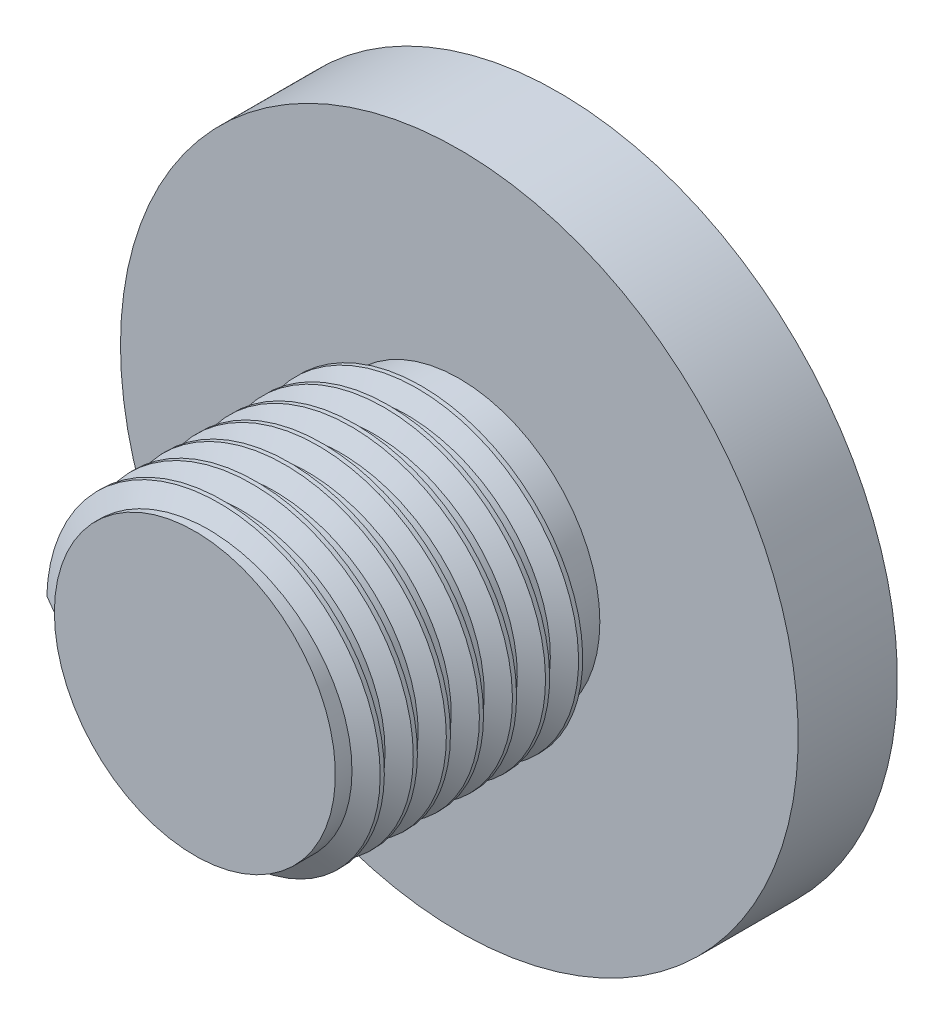
SolidWorks part; units mm, degrees
ref_plane "Plan de face" through (0, 0, 0) normal (0, 0, 1) x (1, 0, 0)
ref_plane "Plan de dessus" through (0, 0, 0) normal (0, 1, 0) x (1, 0, 0)
ref_plane "Plan de droite" through (0, 0, 0) normal (1, 0, 0) x (0, 0, -1)
sketch "Sketch1" plane through (0, 0, 0) normal (0, 0, 1) x (1, 0, 0)
  circle A0 centre (0, 0) radius 4.25
  dimension "D1" = 8.5
extrude "Boss-Extrude1" add sketch "Sketch1" along normal blind 8
sketch "Sketch2" plane through (0, 0, 0) normal (0, 0, -1) x (-1, 0, 0)
  circle A0 centre (0, 0) radius 10.25
  circle A1 centre (0, 0) radius 4.25 construction
  dimension "D1" = 6
extrude "Boss-Extrude2" add sketch "Sketch2" along normal blind 3
thread "Thread1" pitch 1 method extrude profile "Thread Profile1" start angle 0, offset 0, length 7, pitch 1, diameter 8.5
ref_plane "Plane1" through (-4.25, 0, 8) normal (0, -1, 0) x (-1, 0, 0)
sketch "Thread Profile1" plane through (-4.25, 0, 8) normal (0, -1, 0) x (-1, 0, 0)
  line L0 (0, 0) -> (0, 1) construction
  line L1 (0, 0) -> (0.5413, 0.3125)
  line L2 (0.5413, 0.3125) -> (0.5413, 0.4375)
  line L3 (0.5413, 0.4375) -> (0, 0.75)
  line L4 (0.5413, 0.375) -> (0, 0.375) construction
  line L11 (0, 0) -> (0, 0.75)
  point P2 (0, 0)
  dimension "Pitch" = 1
  dimension "Profile_Angle" = 60
  dimension "Profile_Land" = 0.125
  dimension "Profile_Height" = 0.5413
